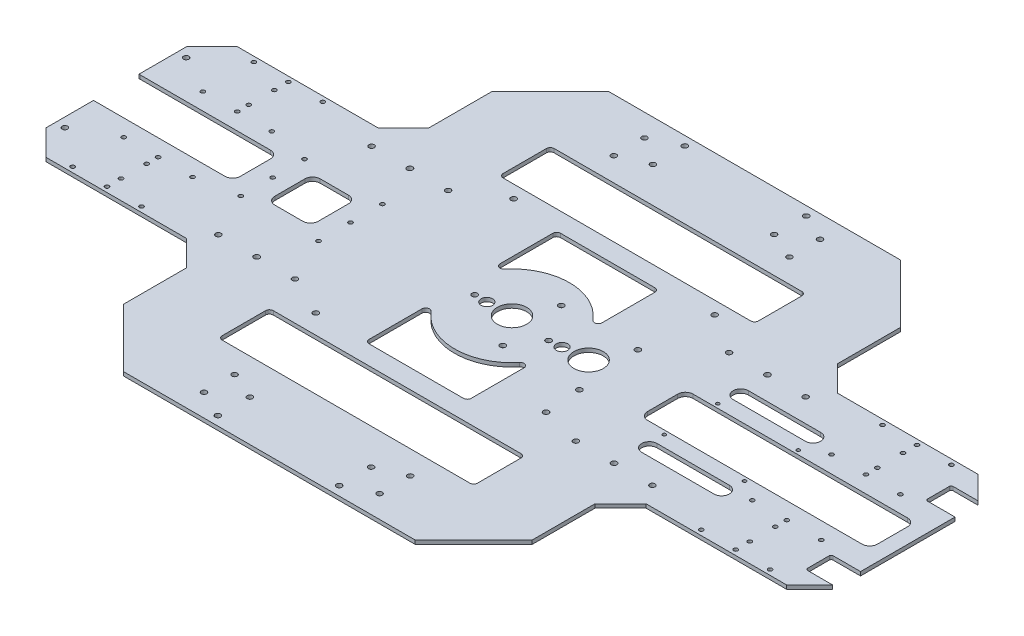
SolidWorks part; units mm, degrees
material "6061 合金"
ref_plane "前视基准面" through (0, 0, 0) normal (0, 0, 1) x (1, 0, 0)
ref_plane "上视基准面" through (0, 0, 0) normal (0, 1, 0) x (1, 0, 0)
ref_plane "右视基准面" through (0, 0, 0) normal (1, 0, 0) x (0, 0, -1)
sketch "草图1" plane through (0, 0, 0) normal (0, 1, 0) x (1, 0, 0)
  line L0 (-310, 75) -> (310, -75) construction
  line L1 (-260, 200) -> (260, 200) construction
  line L2 (-260, 200) -> (-260, -200) construction
  line L3 (-260, -200) -> (260, -200) construction
  line L4 (260, 200) -> (260, -200) construction
  line L5 (310, 75) -> (-310, -75) construction
  line L6 (-160, 200) -> (160, -200) construction
  line L7 (-310, -75) -> (-160, -75)
  line L8 (-310, -75) -> (-310, 75)
  line L9 (-310, 75) -> (-160, 75)
  line L10 (310, -75) -> (310, 75)
  line L11 (160, 200) -> (-160, -200) construction
  line L13 (-160, -200) -> (160, -200)
  line L14 (-160, -200) -> (-160, -75)
  line L15 (-160, 200) -> (160, 200)
  line L16 (160, -200) -> (160, -75)
  line L19 (-160, 75) -> (-160, 200)
  line L22 (160, 75) -> (310, 75)
  line L25 (160, 75) -> (160, 200)
  line L28 (160, -75) -> (310, -75)
  point P0 (0, 0)
  point P6 (-0.5159, 0.1248)
  point P11 (0, 0)
  dimension "D1" = 520
  dimension "D2" = 400
  dimension "D3" = 50
  dimension "D4" = 125
  dimension "D5" = 100
extrude "凸台-拉伸1" add sketch "草图1" along normal blind 3
chamfer "倒角1" distance 20 angle 45 8 edges at (-160, 1.5, -75) (-310, 1.5, -75) (-310, 1.5, 75) (-160, 1.5, 75) (160, 1.5, 75) (160, 1.5, -75) (310, 1.5, 75) (310, 1.5, -75)
sketch "草图2" plane through (0, 3, 0) normal (0, 1, 0) x (1, 0, 0)
  line L0 (-160, 200) -> (-160, 95) construction
  line L1 (-160, 180) -> (160, 180)
  line L2 (-160, 180) -> (-160, 200)
  line L3 (-160, 200) -> (160, 200)
  line L4 (160, 180) -> (160, 200)
  line L6 (160, -200) -> (-160, -200)
  line L7 (160, -200) -> (160, -180)
  line L8 (160, -180) -> (-160, -180)
  line L9 (-160, -200) -> (-160, -180)
  dimension "D1" = 20
  dimension "D2" = 20
extrude "切除-拉伸1" cut sketch "草图2" against normal blind 5
chamfer "倒角2" distance 50 angle 45 4 edges at (-160, 1.5, -180) (-160, 1.5, 180) (160, 1.5, -180) (160, 1.5, 180)
sketch "草图3" plane through (0, 3, 0) normal (0, 1, 0) x (1, 0, 0)
  line L0 (0, 0) -> (144.0598, 0) construction
  line L1 (110, -180) -> (-110, -180) construction
  circle A0 centre (-327.7002, 47.5) radius 2.1
  circle A1 centre (-302.7002, 47.5) radius 2.1
  circle A2 centre (-47.5, 182.8263) radius 2.1
  circle A3 centre (-47.5, 157.8263) radius 2.1
  circle A4 centre (47.5, 182.8263) radius 2.1
  circle A5 centre (47.5, 157.8263) radius 2.1
  circle A6 centre (302.7002, 47.5) radius 2.1
  circle A7 centre (327.7002, 47.5) radius 2.1
  circle A8 centre (-68.75, 172.5) radius 2.1
  circle A9 centre (-68.75, 148.5) radius 2.1
  circle A10 centre (68.75, 172.5) radius 2.1
  circle A11 centre (68.75, 148.5) radius 2.1
  circle A12 centre (68.75, -148.5) radius 2.1
  circle A13 centre (68.75, -172.5) radius 2.1
  circle A14 centre (-68.75, -148.5) radius 2.1
  circle A15 centre (-68.75, -172.5) radius 2.1
  circle A16 centre (327.7002, -47.5) radius 2.1
  circle A17 centre (302.7002, -47.5) radius 2.1
  circle A18 centre (47.5, -157.8263) radius 2.1
  circle A19 centre (47.5, -182.8263) radius 2.1
  circle A20 centre (-47.5, -157.8263) radius 2.1
  circle A21 centre (-47.5, -182.8263) radius 2.1
  circle A22 centre (-302.7002, -47.5) radius 2.1
  circle A23 centre (-327.7002, -47.5) radius 2.1
  dimension "D1" = 4.2
  dimension "D2" = 4.2
  dimension "D3" = 4.2
  dimension "D4" = 4.2
  dimension "D5" = 4.2
  dimension "D6" = 4.2
  dimension "D7" = 4.2
  dimension "D8" = 4.2
  dimension "D9" = 180
extrude "切除-拉伸2" cut sketch "草图3" against normal blind 80
sketch "草图4" plane through (0, 0, 0) normal (0, -1, 0) x (1, 0, 0)
  circle A0 centre (-78.74, 74.91) radius 2.15
  circle A2 centre (-78.74, -80.01) radius 2.15
  circle A3 centre (78.74, -80.01) radius 2.15
  circle A4 centre (78.74, 52.07) radius 2.15
  point P2 (0, 0)
  point P3 (0, 0)
  point P4 (0, 0)
  point P14 (0, 0)
  point P15 (0, 0)
  dimension "D1" = 4.3
  dimension "D2" = 4.3
  dimension "D3" = 4.3
  dimension "D4" = 4.3
extrude "切除-拉伸3" cut sketch "草图4" against normal blind 10
sketch "草图5" plane through (0, 3, 0) normal (0, 1, 0) x (1, 0, 0)
  line L0 (0, 0) -> (90.3311, 0) construction
  line L1 (0, 0) -> (0, 46.0052) construction
  circle A0 centre (219.2002, 71) radius 1.6
  circle A1 centre (273.2002, 71) radius 1.6
  circle A2 centre (246.2002, 71) radius 1.6
  circle A3 centre (219.2002, 30.9984) radius 1.6
  circle A4 centre (246.2002, 30.9984) radius 1.6
  circle A5 centre (273.2002, 30.9984) radius 1.6
  circle A6 centre (246.2002, 60) radius 1.6
  circle A7 centre (246.2002, 40) radius 1.6
  circle A8 centre (246.2002, -40) radius 1.6
  circle A9 centre (246.2002, -60) radius 1.6
  circle A10 centre (273.2002, -30.9984) radius 1.6
  circle A11 centre (246.2002, -30.9984) radius 1.6
  circle A12 centre (219.2002, -30.9984) radius 1.6
  circle A13 centre (246.2002, -71) radius 1.6
  circle A14 centre (273.2002, -71) radius 1.6
  circle A15 centre (219.2002, -71) radius 1.6
  circle A16 centre (-219.2002, -71) radius 1.6
  circle A17 centre (-273.2002, -71) radius 1.6
  circle A18 centre (-246.2002, -71) radius 1.6
  circle A19 centre (-219.2002, -30.9984) radius 1.6
  circle A20 centre (-246.2002, -30.9984) radius 1.6
  circle A21 centre (-273.2002, -30.9984) radius 1.6
  circle A22 centre (-246.2002, -60) radius 1.6
  circle A23 centre (-246.2002, -40) radius 1.6
  circle A24 centre (-246.2002, 40) radius 1.6
  circle A25 centre (-246.2002, 60) radius 1.6
  circle A26 centre (-273.2002, 30.9984) radius 1.6
  circle A27 centre (-246.2002, 30.9984) radius 1.6
  circle A28 centre (-219.2002, 30.9984) radius 1.6
  circle A29 centre (-246.2002, 71) radius 1.6
  circle A30 centre (-273.2002, 71) radius 1.6
  circle A31 centre (-219.2002, 71) radius 1.6
  circle A32 centre (170, -60) radius 2.1
  circle A34 centre (110, -60) radius 2.1
  circle A35 centre (140, -60) radius 2.2
  circle A36 centre (140, 60) radius 2.2
  circle A37 centre (110, 60) radius 2.1
  circle A38 centre (170, 60) radius 2.1
  circle A39 centre (-170, 60) radius 2.1
  circle A40 centre (-110, 60) radius 2.1
  circle A41 centre (-140, 60) radius 2.2
  circle A42 centre (-140, -60) radius 2.2
  circle A43 centre (-110, -60) radius 2.1
  circle A44 centre (-170, -60) radius 2.1
  dimension "D1" = 3.2
extrude "切除-拉伸4" cut sketch "草图5" against normal blind 29
sketch "草图6" plane through (0, 3, 0) normal (0, 1, 0) x (1, 0, 0)
  line L0 (160, -150) -> (160, -95) construction
  line L1 (0, 0) -> (166.252, 0) construction
  line L2 (-160, 130) -> (-110, 180)
  line L3 (110, 180) -> (-110, 180)
  line L4 (110, 180) -> (160, 130)
  line L5 (-160, -95) -> (-160, -150) construction
  line L12 (160, -144.1421) -> (160, -130)
  line L13 (114.1421, -190) -> (160, -144.1421)
  line L14 (52.4797, -190) -> (114.1421, -190)
  line L15 (-114.1421, -190) -> (-52, -190)
  line L16 (-160, -144.1421) -> (-114.1421, -190)
  line L17 (-160, -130) -> (-160, -144.1421)
  line L25 (-52, -190) -> (52.4797, -190)
  line L28 (110, -180) -> (160, -130) construction
  line L29 (110, -180) -> (-110, -180) construction
  line L30 (-160, -130) -> (-110, -180) construction
  line L31 (110, -180) -> (160, -130)
  line L32 (110, -180) -> (-110, -180)
  line L33 (-160, -130) -> (-110, -180)
  line L37 (-52, 190) -> (52.4797, 190)
  line L38 (-160, 130) -> (-160, 144.1421)
  line L39 (-160, 144.1421) -> (-114.1421, 190)
  line L40 (-114.1421, 190) -> (-52, 190)
  line L41 (52.4797, 190) -> (114.1421, 190)
  line L42 (114.1421, 190) -> (160, 144.1421)
  line L43 (160, 144.1421) -> (160, 130)
  dimension "D1" = 10
  dimension "D2" = 10
  dimension "D3" = 10
extrude "凸台-拉伸2" add sketch "草图6" against normal blind 3 contours L2 | L33 L17 L16 L15 L25 L14 L13 L12 L31 L32 region at (-156.7442, 3, -137.0711) region at (134.7689, 3, 164.7689)
sketch "草图7" plane through (0, 3, 0) normal (0, 1, 0) x (1, 0, 0)
  line L0 (310, -55) -> (310, 55) construction
  line L1 (310, 37) -> (287, 37)
  line L2 (310, 37) -> (310, 57)
  line L3 (310, 57) -> (287, 57)
  line L4 (287, 37) -> (287, 57)
  line L5 (290, 75) -> (180, 75) construction
  line L6 (310, -37) -> (287, -37)
  line L7 (310, -37) -> (310, -57)
  line L8 (310, -57) -> (287, -57)
  line L9 (287, -37) -> (287, -57)
  line L10 (180, -75) -> (290, -75) construction
  dimension "D1" = 18
  dimension "D2" = 20
  dimension "D3" = 20
  dimension "D4" = 18
  dimension "D5" = 23
extrude "切除-拉伸5" cut sketch "草图7" against normal blind 3
fillet "圆角1" radius 1.5 4 edges at (287, 1.5, 37) (287, 1.5, 57) (287, 1.5, -37) (287, 1.5, -57)
sketch "草图9" plane through (0, 0, 0) normal (0, -1, 0) x (1, 0, 0)
  line L0 (-45.449, 182.8784) -> (-49.551, 182.8784) construction
  line L1 (49.551, 182.8784) -> (45.449, 182.8784) construction
  line L2 (0, 0) -> (154.6544, 0) construction
  circle A0 centre (-47.5, 182.8784) radius 2.15
  circle A1 centre (47.5, 182.8784) radius 2.15
  circle A2 centre (47.5, -182.8784) radius 2.15
  circle A3 centre (-47.5, -182.8784) radius 2.15
  dimension "D1" = 4.3
extrude "切除-拉伸6" cut sketch "草图9" against normal blind 3
sketch "草图10" plane through (0, 0, 0) normal (0, -1, 0) x (1, 0, 0)
  circle A0 centre (60, 0) radius 11.5
  circle A1 centre (40.8185, 1.6223) radius 4.5
  circle A2 centre (72.3318, -26.2474) radius 2.15
  circle A3 centre (76.565, 23.8034) radius 2.15
  circle A4 centre (31.1032, 2.4441) radius 2.15
  dimension "D1" = 4.3
  dimension "D2" = 23
  dimension "D3" = 9
extrude "切除-拉伸7" cut sketch "草图10" against normal blind 5
sketch "草图11" plane through (0, 0, 0) normal (0, -1, 0) x (1, 0, 0)
  line L0 (-290, 75) -> (-180, 75) construction
  line L2 (-187.4745, 25) -> (-126.5, 25) construction
  line L3 (-187.4745, 25) -> (-187.4745, -25) construction
  line L4 (-187.4745, -25) -> (-126.5, -25) construction
  line L5 (-126.5, 25) -> (-126.5, -25) construction
  line L6 (-187.4745, 25) -> (-126.5, 25) construction
  line L7 (-187.4745, 25) -> (-187.4745, 0) construction
  line L8 (-187.4745, 0) -> (-126.5, 0) construction
  line L9 (-126.5, 25) -> (-126.5, 0) construction
  circle A6 centre (-126.5, -25) radius 1.6
  circle A7 centre (-187.5, -25) radius 1.6
  circle A8 centre (-126.5, 0) radius 1.6
  circle A9 centre (-187.4745, 0) radius 1.6
  circle A10 centre (-187.4745, 25) radius 1.6
  circle A11 centre (-126.5, 25) radius 1.6
  dimension "D1" = 50
  dimension "D2" = 25
  dimension "D3" = 60.9745
extrude "切除-拉伸8" cut sketch "草图11" against normal blind 10
sketch "草图12" plane through (0, 0, 0) normal (0, -1, 0) x (1, 0, 0)
  circle A0 centre (60, 0) radius 140
  dimension "D1" = 280
sketch "草图13" plane through (0, 3, 0) normal (0, 1, 0) x (1, 0, 0)
  line L0 (143.4002, 35.8) -> (200.0002, 35.8) construction
  line L1 (143.4002, 41.8) -> (200.0002, 41.8)
  line L2 (143.4002, 29.8) -> (200.0002, 29.8)
  line L3 (143.4002, -35.8) -> (200.0002, -35.8) construction
  line L4 (143.4002, -29.8) -> (200.0002, -29.8)
  line L5 (143.4002, -41.8) -> (200.0002, -41.8)
  line L6 (137.4002, 15.5) -> (137.4002, 21) construction
  line L7 (206.0002, -21) -> (206.0002, 21) construction
  line L8 (137.4002, -21) -> (137.4002, -15.5) construction
  line L9 (140.2002, 23.8) -> (203.2002, 23.8) construction
  line L10 (140.2002, -23.8) -> (203.2002, -23.8) construction
  circle A0 centre (140.2002, 21) radius 1.35
  circle A1 centre (203.2002, 21) radius 1.35
  circle A2 centre (203.2002, -21) radius 1.35
  circle A3 centre (140.2002, -21) radius 1.35
  arc A4 (143.4002, 41.8) -> (143.4002, 29.8) centre (143.4002, 35.8) ccw
  arc A5 (200.0002, 29.8) -> (200.0002, 41.8) centre (200.0002, 35.8) ccw
  arc A6 (143.4002, -29.8) -> (143.4002, -41.8) centre (143.4002, -35.8) ccw
  arc A7 (200.0002, -41.8) -> (200.0002, -29.8) centre (200.0002, -35.8) ccw
  point P14 (171.7002, 35.8)
  point P19 (171.7002, -35.8)
  dimension "D3" = 6
  dimension "D6" = 6
  dimension "D1" = 6
  dimension "D2" = 6
  dimension "D4" = 6
  dimension "D5" = 6
  dimension "D7" = 6
  dimension "D8" = 6
extrude "切除-拉伸9" cut sketch "草图13" against normal blind 3
sketch "草图14" plane through (0, 3, 0) normal (0, 1, 0) x (1, 0, 0)
  line L0 (143.4002, 29.8) -> (200.0002, 29.8) construction
  line L1 (292, 17.8) -> (124, 17.8)
  line L2 (298, 11.8) -> (298, -11.8)
  line L3 (292, -17.8) -> (124, -17.8)
  line L4 (118, 11.8) -> (118, -11.8)
  line L5 (200.0002, -29.8) -> (143.4002, -29.8) construction
  line L6 (310, -37) -> (310, 37) construction
  arc A0 (292, 17.8) -> (298, 11.8) centre (292, 11.8) cw
  arc A1 (298, -11.8) -> (292, -17.8) centre (292, -11.8) cw
  arc A2 (124, -17.8) -> (118, -11.8) centre (124, -11.8) cw
  arc A3 (124, 17.8) -> (118, 11.8) centre (124, 11.8) ccw
  point P12 (298, 17.8)
  point P19 (118, 17.8)
  dimension "D5" = 6
  dimension "D1" = 12
  dimension "D2" = 12
  dimension "D3" = 12
  dimension "D4" = 180
extrude "切除-拉伸10" cut sketch "草图14" against normal blind 3
sketch "草图15" plane through (0, 3, 0) normal (0, 1, 0) x (1, 0, 0)
  line L0 (60, 0) -> (-109.9354, 0) construction
  line L1 (72.3318, 26.2474) -> (-47.4576, 26.2474) construction
  line L2 (76.565, -23.8034) -> (-55.7658, -23.8034) construction
  line L3 (40.8185, -1.6223) -> (-96.5262, 0.8923) construction
  circle A0 centre (76.565, -23.8034) radius 2.15 construction
  circle A1 centre (72.3318, 26.2474) radius 2.15 construction
  circle A2 centre (31.1032, -2.4441) radius 2.15 construction
  circle A3 centre (40.8185, -1.6223) radius 4.5 construction
  circle A4 centre (60, 0) radius 11.5 construction
  circle A5 centre (76.565, -23.8034) radius 2.15
  circle A6 centre (72.3318, 26.2474) radius 2.15
  circle A7 centre (31.1032, -2.4441) radius 2.15
  circle A8 centre (40.8185, -1.6223) radius 4.5
  circle A9 centre (60, 0) radius 11.5
  circle A10 centre (16.565, -23.8034) radius 2.15
  circle A11 centre (12.3318, 26.2474) radius 2.15
  circle A12 centre (-28.8968, -0.3459) radius 2.15
  circle A13 centre (-19.1815, -0.5238) radius 4.5
  circle A14 centre (0, 0) radius 11.5
  dimension "D1" = 60
  dimension "D2" = 60
  dimension "D3" = 60
  dimension "D4" = 60
  dimension "D5" = 60
extrude "切除-拉伸11" cut sketch "草图15" against normal blind 3
sketch "草图16" plane through (0, 3, 0) normal (0, 1, 0) x (1, 0, 0)
  line L2 (-114.1421, 190) -> (114.1421, 190) construction
  line L7 (-97, 130) -> (97, 130)
  line L8 (-100, 127) -> (-100, 93)
  line L44 (-97, 90) -> (-40, 90)
  line L45 (-40, -90) -> (40, -90)
  line L53 (100, 127) -> (100, 93)
  line L70 (-40, 130) -> (40, 130)
  line L71 (-40, 72) -> (-40, 30.5778)
  line L72 (-40, -130) -> (40, -130)
  line L73 (40, 72) -> (40, 30.5778)
  line L74 (-97, -90) -> (-40, -90)
  line L75 (-100, -93) -> (-100, -127)
  line L76 (-97, -130) -> (97, -130)
  line L77 (100, -93) -> (100, -127)
  line L78 (-114.1421, -190) -> (114.1421, -190) construction
  line L79 (160, 95) -> (160, 144.1421) construction
  line L80 (-160, 144.1421) -> (-160, 95) construction
  line L81 (40, 90) -> (97, 90)
  line L82 (-40, -30.5778) -> (-40, -72)
  line L83 (40, -30.5778) -> (40, -72)
  line L84 (40, -90) -> (97, -90)
  line L85 (-37, -75) -> (37, -75)
  line L87 (-40, 90) -> (40, 90)
  line L89 (-37, 75) -> (37, 75)
  arc A56 (-34.6875, -28.6667) -> (34.6875, -28.6667) centre (0, 0) ccw
  arc A57 (34.6875, 28.6667) -> (-34.6875, 28.6667) centre (0, 0) ccw
  arc A58 (-40, -72) -> (-37, -75) centre (-37, -72) ccw
  arc A59 (37, -75) -> (40, -72) centre (37, -72) ccw
  arc A60 (97, -130) -> (100, -127) centre (97, -127) ccw
  arc A61 (97, -90) -> (100, -93) centre (97, -93) cw
  arc A62 (-100, -127) -> (-97, -130) centre (-97, -127) ccw
  arc A63 (-97, -90) -> (-100, -93) centre (-97, -93) ccw
  arc A64 (-100, 93) -> (-97, 90) centre (-97, 93) ccw
  arc A65 (-97, 130) -> (-100, 127) centre (-97, 127) ccw
  arc A66 (97, 130) -> (100, 127) centre (97, 127) cw
  arc A67 (97, 90) -> (100, 93) centre (97, 93) ccw
  arc A68 (37, 75) -> (40, 72) centre (37, 72) cw
  arc A69 (-40, 72) -> (-37, 75) centre (-37, 72) cw
  arc A70 (-34.6875, -28.6667) -> (-40, -30.5778) centre (-37, -30.5778) ccw
  arc A71 (40, -30.5778) -> (34.6875, -28.6667) centre (37, -30.5778) ccw
  arc A72 (40, 30.5778) -> (34.6875, 28.6667) centre (37, 30.5778) cw
  arc A73 (-34.6875, 28.6667) -> (-40, 30.5778) centre (-37, 30.5778) cw
  point P39 (100, -130)
  point P42 (100, -90)
  point P53 (100, 130)
  point P56 (100, 90)
  point P63 (-40, -20.6155)
  point P68 (40, 20.6155)
  dimension "D5" = 60
  dimension "D11" = 90
  dimension "D14" = 3
  dimension "D1" = 60
  dimension "D2" = 60
  dimension "D3" = 60
  dimension "D4" = 60
  dimension "D6" = 60
  dimension "D7" = 60
  dimension "D8" = 60
  dimension "D9" = 40
  dimension "D10" = 40
  dimension "D12" = 15
  dimension "D13" = 15
extrude "切除-拉伸12" cut sketch "草图16" against normal blind 3 contours L81 A67 L53 A66 L7 A65 L8 A64 L44 L87 | A73 A57 A72 L73 A68 L89 A69 L71 | L83 A71 A56 A70 L82 A58 L85 A59 | L74 A63 L75 A62 L76 L72 A60 L77 A61 L84 L45 region at (0, 3, -110) region at (0, 3, 110) region at (0, 3, -56.2095) region at (0, 3, 56.2095)
sketch "草图17" plane through (0, 3, 0) normal (0, 1, 0) x (1, 0, 0)
  line L1 (-308.8279, 17.8) -> (-207, 17.8)
  line L2 (-314.8279, 11.8) -> (-314.8279, -11.8)
  line L3 (-308.8279, -17.8) -> (-207, -17.8)
  line L4 (-201, 11.8) -> (-201, -11.8)
  line L5 (-168, 17.8) -> (-146, 17.8)
  line L6 (-174, 11.8) -> (-174, -11.8)
  line L7 (-168, -17.8) -> (-146, -17.8)
  line L8 (-140, 11.8) -> (-140, -11.8)
  line L14 (-326.8279, 33.3431) -> (-326.8279, -33.3431) construction
  arc A4 (-146, 17.8) -> (-140, 11.8) centre (-146, 11.8) cw
  arc A5 (-146, -17.8) -> (-140, -11.8) centre (-146, -11.8) ccw
  arc A6 (-174, -11.8) -> (-168, -17.8) centre (-168, -11.8) ccw
  arc A7 (-168, 17.8) -> (-174, 11.8) centre (-168, 11.8) ccw
  arc A8 (-207, 17.8) -> (-201, 11.8) centre (-207, 11.8) cw
  arc A9 (-207, -17.8) -> (-201, -11.8) centre (-207, -11.8) ccw
  arc A10 (-314.8279, -11.8) -> (-308.8279, -17.8) centre (-308.8279, -11.8) ccw
  arc A11 (-308.8279, 17.8) -> (-314.8279, 11.8) centre (-308.8279, 11.8) ccw
  dimension "D1" = 12
extrude "切除-拉伸13" cut sketch "草图17" against normal blind 3
